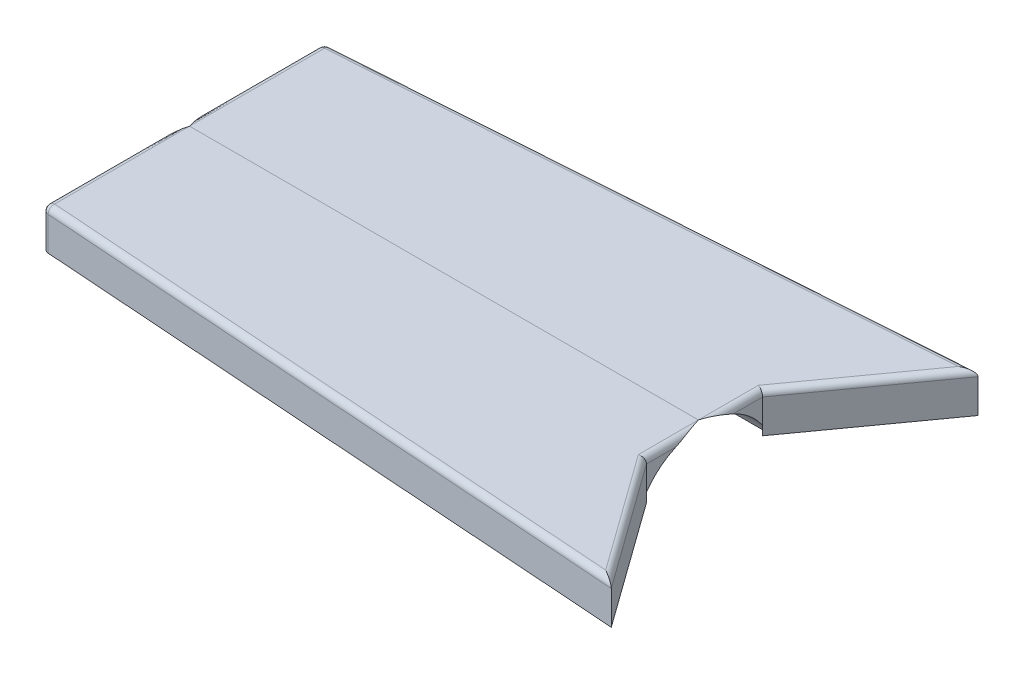
SolidWorks part; units mm, degrees
ref_plane "Front Plane" through (0, 0, 0) normal (0, 0, 1) x (1, 0, 0)
ref_plane "Top Plane" through (0, 0, 0) normal (0, 1, 0) x (1, 0, 0)
ref_plane "Right Plane" through (0, 0, 0) normal (1, 0, 0) x (0, 0, -1)
sketch "Sketch1" plane through (0, 0, 0) normal (1, 0, 0) x (0, 0, -1)
  line L0 (11.5, -5) -> (11.5, 6.5) construction
  arc A0 (21.8562, 0) -> (1.1438, 0) centre (11.5, -5) ccw construction
  arc A1 (21.8562, 0) -> (1.1438, 0) centre (11.5, -5) ccw construction
ref_plane "Plane1" through (0, 6.5, 0) normal (0, 1, 0) x (1, 0, 0)
sketch "Sketch2" plane through (0, 6.5, 0) normal (0, 1, 0) x (1, 0, 0)
  line L0 (74.2942, -3.9682) -> (84.75, -18.5) construction
  line L1 (74.2942, -3.9682) -> (84.75, -18.5) construction
  line L2 (84.75, 41.5) -> (74.2942, 26.9682) construction
  line L3 (84.75, 41.5) -> (74.2942, 26.9682) construction
  line L4 (84.75, 41.5) -> (-15.25, 34.5)
  line L5 (-15.25, 34.5) -> (-15.25, -11.5)
  line L6 (84.75, -18.5) -> (-15.25, -11.5)
  line L7 (84.75, 41.5) -> (70, 21)
  line L8 (70, 21) -> (70, 2)
  line L9 (70, 2) -> (84.75, -18.5)
  dimension "D1" = 46
  dimension "D2" = 100
  dimension "D3" = 7
extrude "Boss-Extrude1" add sketch "Sketch2" against normal blind 6.5
sketch "Sketch4" plane through (70, 0, 0) normal (1, 0, 0) x (0, 0, -1)
  circle A0 centre (11.5, -5) radius 11.5
  dimension "D1" = 23
extrude "Cut-Extrude1" cut sketch "Sketch4" against normal through all
fillet "Fillet1" radius 1 4 edges at (77.375, 6.5, 8.25) (70, 6.5, -6.75) (-15.25, 6.5, 0) (34.75, 6.5, 15)
fillet "Fillet2" radius 1 4 edges at (70, 6.5, -16.25) (77.375, 6.5, -31.25) (34.75, 6.5, -38) (-15.25, 6.5, -23)
sketch "Sketch5" plane through (0, 0, 0) normal (0, -1, 0) x (1, 0, 0)
  line L0 (-15.25, -34.5) -> (-15.25, -21.8562) construction
  line L1 (-15.25, -32) -> (8.75, -32)
  line L2 (-15.25, -32) -> (-15.25, -23)
  line L3 (-15.25, -23) -> (8.75, -23)
  line L4 (8.75, -32) -> (8.75, -23) construction
  line L5 (-15.25, -1.1438) -> (-15.25, 11.5) construction
  line L6 (-15.25, 8.9682) -> (8.75, 8.9682)
  line L7 (-15.25, 8.9682) -> (-15.25, -0.0318)
  line L8 (-15.25, -0.0318) -> (8.75, -0.0318)
  line L9 (8.75, 8.9682) -> (8.75, -0.0318) construction
  line L10 (8.75, 8.9682) -> (11.25, 8.9682)
  line L11 (11.25, 8.9682) -> (11.25, -0.0318)
  line L12 (8.75, -0.0318) -> (70, -0.0318) construction
  line L13 (11.25, -0.0318) -> (8.75, -0.0318)
  line L14 (8.75, -32) -> (11.25, -32)
  line L15 (11.25, -32) -> (11.25, -22.9682)
  line L16 (8.75, -22.9682) -> (70, -22.9682) construction
  line L17 (11.25, -22.9682) -> (8.75, -23)
  dimension "D1" = 9
  dimension "D2" = 9
  dimension "D3" = 2.5
  dimension "D4" = 2.5
extrude "Cut-Extrude2" cut sketch "Sketch5" against normal blind 2.5
fillet "Fillet3" radius 1 2 edges at (-14.9571, 6.2071, -34.2269) (-15.25, 2.75, -34.5)
fillet "Fillet4" radius 1 2 edges at (-14.9571, 6.2071, 11.2269) (-15.25, 2.75, 11.5)
